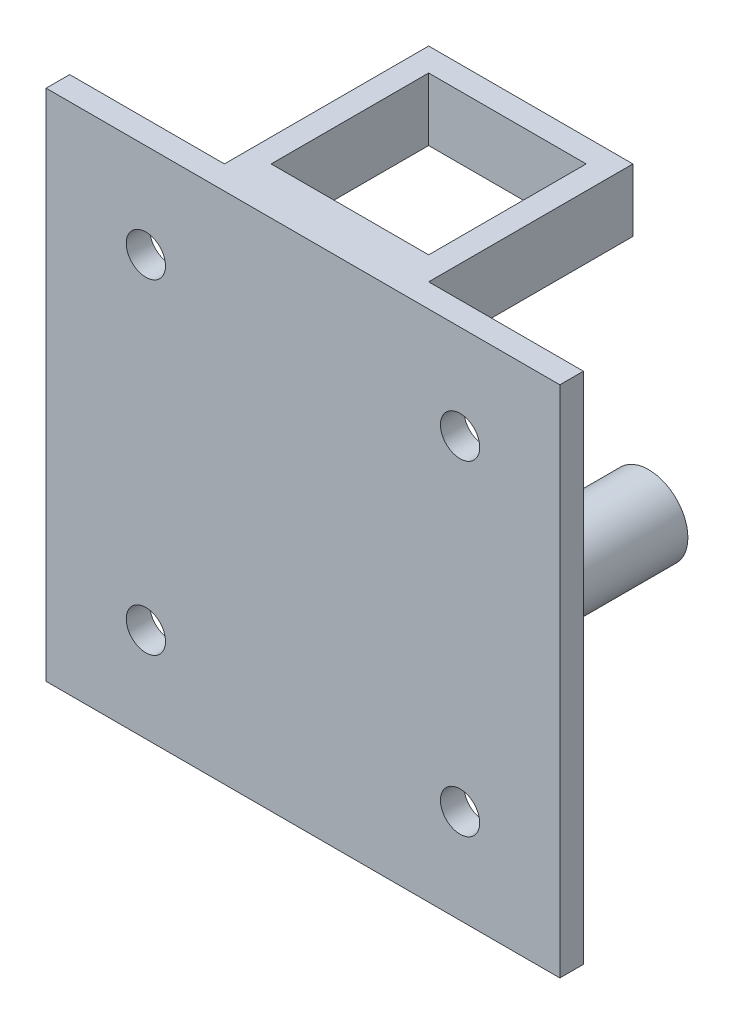
SolidWorks part; units mm, degrees
ref_plane "Спереди" through (0, 0, 0) normal (0, 0, 1) x (1, 0, 0)
ref_plane "Сверху" through (0, 0, 0) normal (0, 1, 0) x (1, 0, 0)
ref_plane "Справа" through (0, 0, 0) normal (1, 0, 0) x (0, 0, -1)
sketch "Эскиз1" plane through (0, 0, 0) normal (0, 0, 1) x (1, 0, 0)
  line L0 (-65.4, 53.4) -> (0, 53.4) construction
  line L1 (0, 0) -> (-65.4, 0)
  line L2 (0, 0) -> (0, 65.4)
  line L3 (0, 65.4) -> (-65.4, 65.4)
  line L4 (-65.4, 0) -> (-65.4, 65.4)
  line L5 (-32.7, 65.4) -> (-32.7, 0) construction
  line L6 (-65.4, 32.7) -> (0, 32.7) construction
  circle A0 centre (-52.7, 53.4) radius 2.5
  circle A2 centre (-12.7, 53.4) radius 2.5
  circle A3 centre (-12.7, 12) radius 2.5
  circle A4 centre (-52.7, 12) radius 2.5
  dimension "D4" = 5
  dimension "D5" = 20
  dimension "D1" = 65.4
  dimension "D2" = 65.4
  dimension "D3" = 12
extrude "каретка" add sketch "Эскиз1" along normal blind 3
sketch "Эскиз2" plane through (0, 0, 0) normal (0, 0, -1) x (-1, 0, 0)
  line L0 (0, 65.4) -> (65.4, 65.4) construction
  line L1 (19.7, 65.4) -> (45.7, 65.4)
  line L2 (19.7, 65.4) -> (19.7, 57.4)
  line L3 (19.7, 57.4) -> (45.7, 57.4)
  line L4 (45.7, 65.4) -> (45.7, 57.4)
  line L5 (32.7, 65.4) -> (32.7, 0) construction
  line L6 (65.4, 0) -> (0, 0) construction
  point P10 (32.7, 65.4)
  dimension "D1" = 8
  dimension "D2" = 26
extrude "крепеж для направляющей" add sketch "Эскиз2" along normal blind 26
sketch "Эскиз3" plane through (0, 57.4, 0) normal (0, -1, 0) x (1, 0, 0)
  line L0 (-45.7, -13) -> (-19.7, -13) construction
  line L1 (-42.725, -2.975) -> (-22.675, -2.975)
  line L2 (-42.725, -2.975) -> (-42.725, -23.025)
  line L3 (-42.725, -23.025) -> (-22.675, -23.025)
  line L4 (-22.675, -2.975) -> (-22.675, -23.025)
  line L5 (-45.7, -26) -> (-45.7, 0) construction
  line L6 (-19.7, -26) -> (-19.7, 0) construction
  line L7 (-42.725, -13) -> (-22.675, -13) construction
  point P12 (-32.7, -13)
  point P13 (-32.7, -13)
  dimension "D1" = 20.05
  dimension "D2" = 20.05
extrude "дырка в крепеже для направляющей" cut sketch "Эскиз3" against normal through all
sketch "Эскиз4" plane through (0, 0, 0) normal (0, 0, -1) x (-1, 0, 0)
  line L0 (12.7, 53.4) -> (12.7, 12) construction
  circle A1 centre (12.7, 32.7) radius 2
  dimension "D1" = 4
sketch "Эскиз5" plane through (0, 0, 0) normal (0, 0, -1) x (-1, 0, 0)
  line L0 (52.7, 53.4) -> (52.7, 12) construction
  circle A0 centre (52.7, 32.7) radius 2.4
  dimension "D1" = 4.8
sketch "Эскиз8" plane through (0, 0, 0) normal (0, 0, -1) x (-1, 0, 0)
  circle A0 centre (52.7, 32.7) radius 5.8726
  dimension "D1" = 11.7451
extrude "Бобышка-Вытянуть1" add sketch "Эскиз8" along normal blind 14.4
extrude "Бобышка-Вытянуть2" add sketch "Эскиз5" along normal blind 30
extrude "Бобышка-Вытянуть3" add sketch "Эскиз4" along normal blind 14.4 contours A1
sketch "Эскиз12" plane through (0, 0, 0) normal (0, 0, -1) x (-1, 0, 0)
  circle A0 centre (12.7, 32.7) radius 5
  dimension "D1" = 10
extrude "Бобышка-Вытянуть5" add sketch "Эскиз12" along normal blind 21 contours A0
sketch "Эскиз13" plane through (0, 0, -21) normal (0, 0, -1) x (-1, 0, 0)
  circle A0 centre (12.7, 32.7) radius 2
  dimension "D1" = 4
extrude "Вырез-Вытянуть1" cut sketch "Эскиз13" against normal blind 6.6
